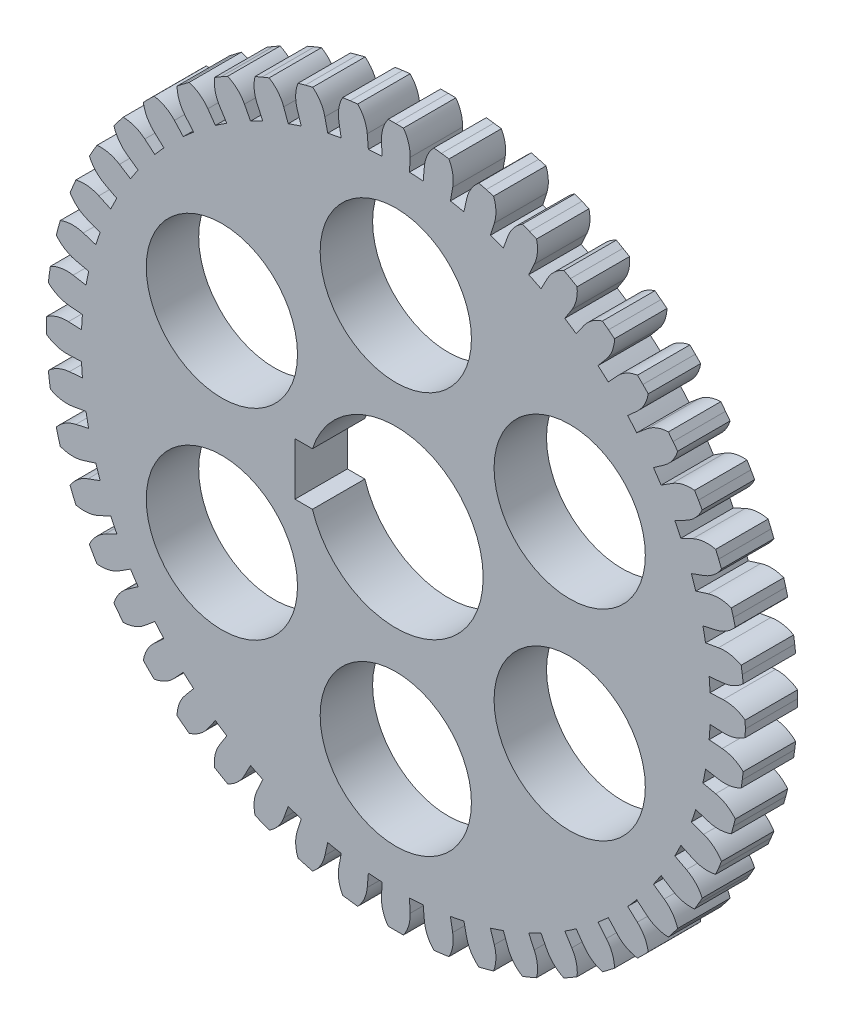
SolidWorks part; units mm, degrees
ref_plane "Plan de face" through (0, 0, 0) normal (0, 0, 1) x (1, 0, 0)
ref_plane "Plan de dessus" through (0, 0, 0) normal (0, 1, 0) x (1, 0, 0)
ref_plane "Plan de droite" through (0, 0, 0) normal (1, 0, 0) x (0, 0, -1)
sketch "Esquisse1" plane through (0, 0, 0) normal (0, 0, 1) x (1, 0, 0)
  line L0 (0, 0) -> (20, 0) construction
  line L1 (0, 0) -> (17.9315, 1.5688) construction
  line L2 (0, 0) -> (19.981, 0.8724) construction
  line L3 (19.981, 0.8724) -> (0, 0) construction
  line L4 (0, 0) -> (19.9952, 0.4363) construction
  line L5 (17.9829, 0.7851) -> (18.7322, 0.8179)
  line L6 (20, 0) -> (19.9952, 0.4363)
  line L7 (17.9829, -0.7851) -> (18.7322, -0.8179)
  line L8 (20, 0) -> (19.9952, -0.4363)
  line L9 (17.9315, 1.5688) -> (0, 0)
  line L10 (0, 0) -> (17.9315, -1.5688)
  circle A0 centre (0, 0) radius 18 construction
  circle A1 centre (0, 0) radius 18.75 construction
  circle A2 centre (0, 0) radius 20 construction
  arc A3 (18.7322, 0.8179) -> (19.9952, 0.4363) centre (18.8192, -1.1754) cw
  arc A4 (17.9315, 1.5688) -> (17.9829, 0.7851) centre (0, 0) cw
  arc A5 (17.9315, -1.5688) -> (17.9829, -0.7851) centre (0, 0) ccw
  arc A6 (18.7322, -0.8179) -> (19.9952, -0.4363) centre (18.8192, 1.1754) ccw
  dimension "D2" = 37.5
  dimension "D3" = 40
  dimension "D1" = 36
  dimension "D4" = 1.25
  dimension "D5" = 2.5
  dimension "D6" = 5
extrude "Boss.-Extru.3" add sketch "Esquisse1" along normal blind 3
pattern_circular "Répétition circulaire1" count 48 over 360 about axis through (0, 0, 3) along (0, 0, -1) of "Boss.-Extru.3"
sketch "Esquisse2" plane through (0, 0, 0) normal (0, 0, -1) x (-1, 0, 0)
  line L0 (0, 5) -> (0, 17.9829) construction
  line L1 (-0.7851, 17.9829) -> (0.7851, 17.9829) construction
  circle A0 centre (0, 0) radius 5
  circle A1 centre (0, 11.4914) radius 4.3276
  circle A2 centre (9.9519, 5.7457) radius 4.3276
  circle A3 centre (9.9519, -5.7457) radius 4.3276
  circle A4 centre (0, -11.4914) radius 4.3276
  circle A5 centre (-9.9519, -5.7457) radius 4.3276
  circle A6 centre (-9.9519, 5.7457) radius 4.3276
  point P13 (0, 11.4914)
  point P33 (0, 0)
  dimension "D1" = 10
  dimension "D3" = 8.6552
  dimension "D2" = 12.9829
  dimension "D4" = 6
extrude "Enlèv. mat.-Extru.1" cut sketch "Esquisse2" against normal up to surface (3 mm away) up to face at (0, 0, 3)
sketch "Esquisse3" plane through (0, 0, 3) normal (0, 0, 1) x (1, 0, 0)
  line L1 (-5.7697, -1.5) -> (-4.7697, -1.5)
  line L2 (-5.7697, -1.5) -> (-5.7697, 1.5)
  line L3 (-5.7697, 1.5) -> (-4.7697, 1.5)
  line L5 (-5.7697, -1.5) -> (-4.7697, 1.5) construction
  line L6 (-5.7697, 1.5) -> (-4.7697, -1.5) construction
  circle A0 centre (0, 0) radius 5 construction
  arc A1 (-4.7697, 1.5) -> (-4.7697, -1.5) centre (0, 0) ccw
  point P0 (-5.2697, 0)
  dimension "D1" = 3
  dimension "D2" = 1
extrude "Enlèv. mat.-Extru.2" cut sketch "Esquisse3" against normal up to surface (3 mm away) up to face at (5.6243, 5.7457, 0)
equation "\"D5@Esquisse1\"=\"D6@Esquisse1\"/2"
equation "\"D4@Esquisse1\"=\"D6@Esquisse1\"/4"
equation "\"D3@Esquisse2\"=2/3 * \"D2@Esquisse2\""
